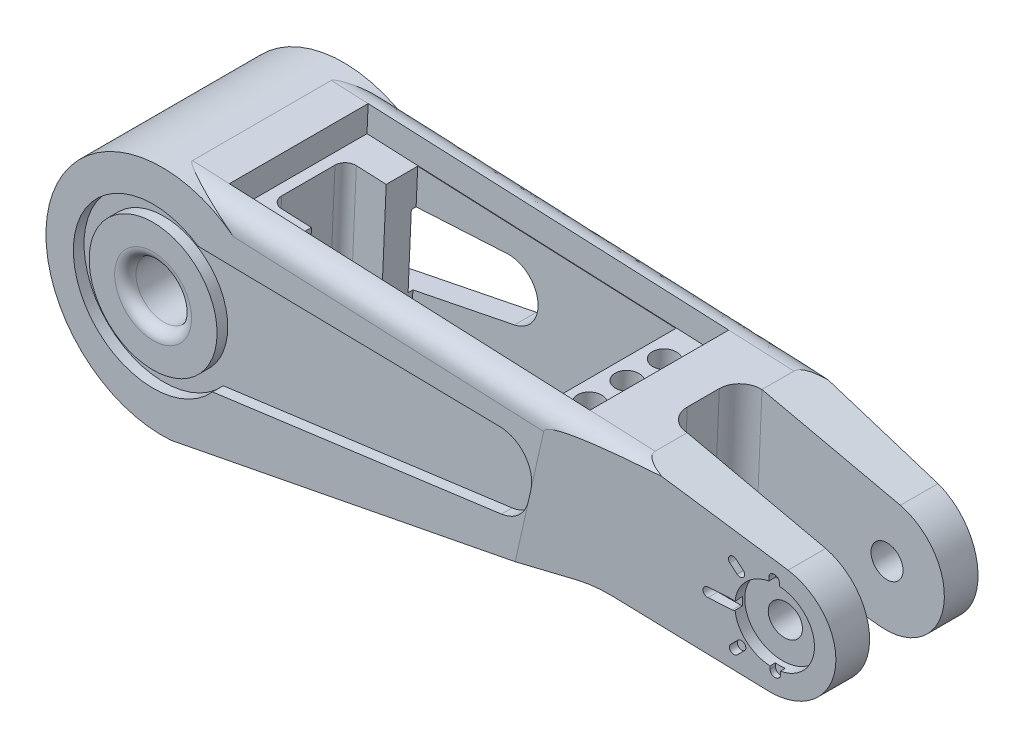
SolidWorks part; units mm, degrees
ref_plane "前视基准面" through (0, 0, 0) normal (0, 0, 1) x (1, 0, 0)
ref_plane "上视基准面" through (0, 0, 0) normal (0, 1, 0) x (1, 0, 0)
ref_plane "右视基准面" through (0, 0, 0) normal (1, 0, 0) x (0, 0, -1)
sketch "草图1" plane through (0, 0, 0) normal (0, 0, 1) x (1, 0, 0)
  line L2 (-19.4532, -0.6445) -> (19.7335, 6.9761)
  line L4 (-19.4532, 21.0492) -> (23.8765, 19.1407)
  line L9 (23.8765, 19.1407) -> (36.8454, 16.2397)
  line L10 (19.7335, 6.9761) -> (35.0831, 5.4643)
  circle A5 centre (-21.1408, 10.2023) radius 2.6 construction
  circle A6 centre (-21.1408, 10.2023) radius 2.6
  circle A7 centre (35.5914, 11.0768) radius 1.5
  arc A13 (35.0831, 5.4643) -> (36.8454, 16.2397) centre (35.4798, 10.9312) ccw
  arc A15 (-19.4532, 21.0492) -> (-19.4532, -0.6445) centre (-20.297, 10.2023) ccw
  dimension "D2" = 3
  dimension "D6" = 5.2
extrude "凸台-拉伸1" add sketch "草图1" along normal blind 17
sketch "草图5" plane through (0.8877, 20.1532, 0) normal (0.044, 0.999, 0) x (0.999, -0.044, 0)
  line L0 (-2.1258, -8.5) -> (9.9742, -8.5) construction
  line L1 (-12.1, -2.05) -> (12.1, -2.05)
  line L2 (-12.1, -2.05) -> (-12.1, -14.95) construction
  line L3 (-12.1, -14.95) -> (12.1, -14.95)
  line L4 (12.1, -2.05) -> (12.1, -14.95)
  line L5 (-12.1, -2.05) -> (12.1, -14.95) construction
  line L6 (-12.1, -14.95) -> (12.1, -2.05) construction
  line L7 (-14, -5) -> (14, -5) construction
  line L8 (-14, -5) -> (-14, -12) construction
  line L9 (-14, -12) -> (14, -12) construction
  line L10 (14, -5) -> (14, -12) construction
  line L11 (-14, -5) -> (14, -12) construction
  line L12 (-14, -12) -> (14, -5) construction
  line L13 (-12.1, -2.05) -> (-12.1, -5)
  line L14 (21.0181, -5) -> (64.762, -5)
  line L15 (21.0181, -5) -> (21.0181, -12)
  line L16 (21.0181, -12) -> (64.762, -12)
  line L17 (64.762, -5) -> (64.762, -12)
  line L18 (21.0181, -5) -> (64.762, -12) construction
  line L19 (21.0181, -12) -> (64.762, -5) construction
  line L20 (-15.9, -5) -> (-12.1, -5)
  line L21 (-15.9, -5) -> (-15.9, -12)
  line L22 (-15.9, -12) -> (-12.1, -12)
  line L23 (-12.1, -5) -> (-12.1, -12) construction
  line L24 (-15.9, -5) -> (-12.1, -12) construction
  line L25 (-15.9, -12) -> (-12.1, -5) construction
  line L26 (-12.1, -12) -> (-12.1, -14.95)
  line L27 (-25.9783, -8.5) -> (-22.2059, -8.5) construction
  circle A0 centre (-14, -5) radius 1.25 construction
  circle A1 centre (-14, -12) radius 1.25 construction
  circle A2 centre (14, -5) radius 1.15
  circle A3 centre (14, -12) radius 1.15
  circle A4 centre (-14, -8.5) radius 1.25 construction
  circle A5 centre (14, -8.5) radius 1.15
  point P0 (0, -8.5)
  point P5 (0, -8.5)
  point P23 (42.89, -8.5)
  dimension "D5" = 2.5
  dimension "D8" = 2.5
  dimension "D9" = 7
  dimension "D1" = 24.2
  dimension "D2" = 12.9
  dimension "D3" = 28
  dimension "D4" = 7
  dimension "D10" = 0
extrude "切除-拉伸2" cut sketch "草图5" against normal through all both and the other way through all
sketch "草图7" plane through (12.0883, -0.5324, 0) normal (-0.999, 0.044, 0) x (0, 0, 1)
  line L0 (2.05, 6.0797) -> (2.05, 20.1728) construction
  line L1 (2.05, 15.1728) -> (14.95, 15.1728)
  line L2 (2.05, 15.1728) -> (2.05, 3.1935)
  line L3 (2.05, 3.1935) -> (14.95, 3.1935)
  line L4 (14.95, 15.1728) -> (14.95, 3.1935)
  line L5 (14.95, 6.0797) -> (14.95, 20.1728) construction
  line L6 (2.05, 20.1728) -> (14.95, 20.1728) construction
  dimension "D1" = 5
extrude "切除-拉伸3" cut sketch "草图7" against normal blind 4
fillet "圆角2" radius 2 2 edges at (2.2116, 20.0949, 0) (2.2116, 20.0949, 17) conic rho 0.5
fillet "圆角3" radius 3 rebuild error yes
sketch "草图8" plane through (5.2154, 23.315, 0) normal (0.2183, 0.9759, 0) x (0.9759, -0.2183, 0)
  line L0 (11.1868, 0) -> (41.8849, -2.1466)
  line L1 (-17.391, 0) -> (30.5415, 0) construction
  line L2 (41.8849, -2.1466) -> (37.5658, 8.2117)
  line L3 (37.5658, 8.2117) -> (11.1868, 0)
  line L4 (11.2348, -17) -> (38.9022, -15.0653)
  line L5 (30.5415, -17) -> (-17.391, -17) construction
  line L6 (38.9022, -15.0653) -> (33.4878, -36.0011)
  line L7 (33.4878, -36.0011) -> (11.2348, -17)
  line L8 (32.4117, -17) -> (30.5415, -17) construction
  line L9 (36.3426, 0) -> (32.0305, 0) construction
  dimension "D1" = 4
  dimension "D2" = 4
extrude "切除-拉伸4" cut sketch "草图8" against normal through all both and the other way through all
sketch "草图9" plane through (0.8877, 20.1532, 0) normal (0.044, 0.999, 0) x (0.999, -0.044, 0)
  line L0 (23.0111, -2) -> (-20.3606, -2) construction
  line L1 (-16.9054, -2) -> (16.8949, -2)
  line L2 (-16.9054, -2) -> (-16.9054, -15)
  line L3 (-16.9054, -15) -> (16.8949, -15)
  line L4 (16.8949, -2) -> (16.8949, -15)
  line L5 (-20.3606, -15) -> (23.0111, -15) construction
extrude "切除-拉伸5" cut sketch "草图9" against normal blind 2.5
sketch "草图10" plane through (0, 0, 0) normal (0, 0, -1) x (-1, 0, 0)
  circle A0 centre (21.1408, 10.2023) radius 3.9889
  circle A1 centre (21.1408, 10.2023) radius 1.15
  dimension "D1" = 2.3
extrude "凸台-拉伸2" add sketch "草图10" against normal blind 9
sketch "草图11" plane through (0, 0, 0) normal (0, 0, -1) x (-1, 0, 0)
  line L4 (2.2472, 9.8443) -> (20.4137, 6.1927)
  line L5 (2.9414, 15.2862) -> (21.1408, 14.2773)
  circle A0 centre (21.1408, 10.2023) radius 4.075 construction
  circle A1 centre (2.7892, 12.5404) radius 2.75 construction
  arc A5 (2.9414, 15.2862) -> (2.2472, 9.8443) centre (2.7892, 12.5404) ccw
  arc A6 (21.1408, 14.2773) -> (20.4137, 6.1927) centre (21.1408, 10.2023) cw
  dimension "D1" = 8.15
  dimension "D3" = 5.5
  dimension "D2" = 18.5
extrude "切除-拉伸6" cut sketch "草图11" against normal blind 2.5
fillet "圆角5" radius 2 2 edges at (21.6121, 13.0232, 5) (21.6121, 13.0232, 12)
sketch "草图13" plane through (0, 0, 2.5) normal (0, 0, -1) x (-1, 0, 0)
  circle A0 centre (21.1408, 10.2023) radius 3.625
  dimension "D1" = 7.25
extrude "切除-拉伸7" cut sketch "草图13" against normal blind 1
fillet "圆角7" radius 1 1 edges at (-18.5408, 10.2023, 17)
fillet "圆角8" radius 11 1 edges at (19.7335, 6.9761, 8.5017)
sketch "草图16" plane through (0, 0, 17) normal (0, 0, 1) x (1, 0, 0)
  line L0 (15.0453, 15.7934) -> (-16.9221, 16.3666)
  line L1 (13.5523, 9.1193) -> (-15.5729, 5.223)
  line L2 (12.77, 5.6219) -> (15.4294, 17.5108) construction
  line L3 (15.0453, 15.7934) -> (13.5523, 9.1193)
  circle A0 centre (-21.1408, 10.2023) radius 5.9907
  circle A1 centre (-21.1408, 10.2023) radius 7.4697 construction
  arc A2 (-16.9221, 16.3666) -> (-15.5729, 5.223) centre (-21.1408, 10.2023) ccw
extrude "切除-拉伸8" cut sketch "草图16" against normal blind 1
fillet "圆角9" radius 3 2 edges at (13.5523, 9.1193, 16.5) (15.0453, 15.7934, 16.5)
sketch "草图17" plane through (1.2078, -0.2702, 17.6991) normal (0.0681, -0.0152, 0.9976) x (0.9977, 0.001, -0.0681)
  circle A0 centre (34.4635, 11.3125) radius 3.5
  dimension "D1" = 7
extrude "切除-拉伸9" cut sketch "草图17" against normal blind 1
sketch "草图18" plane through (0.0531, -0.0119, -0.7785) normal (0.0681, -0.0152, -0.9976) x (-0.9977, -0.001, -0.0681)
  circle A0 centre (-35.6209, 11.0529) radius 3.5
  dimension "D1" = 7
extrude "切除-拉伸10" cut sketch "草图18" against normal blind 1
fillet "圆角10" radius 1 2 edges at (-15.5102, 9.1996, 5) (-15.5102, 9.1996, 12)
sketch "草图19" plane through (0, 0, 16) normal (0, 0, 1) x (1, 0, 0)
  line L0 (-21.1408, 10.2023) -> (35.5981, 10.2023) construction
  line L1 (35.5981, 10.2023) -> (35.5981, 22.1291) construction
  line L2 (31.8727, 11.094) -> (29.7419, 11.094) construction
  line L3 (31.8727, 10.6598) -> (29.7419, 10.6598)
  line L4 (31.8727, 11.5282) -> (29.7419, 11.5282)
  line L5 (35.5981, 14.8624) -> (35.5981, 7.3257) construction
  line L6 (36.0598, 14.8624) -> (36.0598, 7.3257)
  line L7 (35.1364, 14.8624) -> (35.1364, 7.3257)
  line L8 (35.5981, 11.094) -> (31.9347, 14.7574) construction
  line L9 (35.5915, 11.0766) -> (32.6922, 8.1772) construction
  line L10 (32.6148, 8.0998) -> (31.9812, 7.4662) construction
  line L11 (32.9054, 7.8092) -> (32.2718, 7.1756)
  line L12 (32.3241, 8.3904) -> (31.6905, 7.7568)
  line L13 (32.6148, 14.0774) -> (31.9873, 14.7048) construction
  line L14 (32.3348, 13.7974) -> (31.7073, 14.4249)
  line L15 (32.8947, 14.3573) -> (32.2672, 14.9848)
  arc A0 (31.8727, 10.6598) -> (31.8727, 11.5282) centre (31.8727, 11.094) ccw
  arc A1 (29.7419, 11.5282) -> (29.7419, 10.6598) centre (29.7419, 11.094) ccw
  arc A2 (36.0598, 14.8624) -> (35.1364, 14.8624) centre (35.5981, 14.8624) ccw
  arc A3 (35.1364, 7.3257) -> (36.0598, 7.3257) centre (35.5981, 7.3257) ccw
  arc A4 (32.9054, 7.8092) -> (32.3241, 8.3904) centre (32.6148, 8.0998) ccw
  arc A5 (31.6905, 7.7568) -> (32.2718, 7.1756) centre (31.9812, 7.4662) ccw
  arc A6 (32.3348, 13.7974) -> (32.8947, 14.3573) centre (32.6148, 14.0774) ccw
  arc A7 (32.2672, 14.9848) -> (31.7073, 14.4249) centre (31.9873, 14.7048) ccw
  point P3 (30.8073, 11.094)
  point P14 (35.5981, 11.094)
  point P26 (32.298, 7.783)
  point P31 (32.301, 14.3911)
  dimension "D1" = 90
  dimension "D2" = 45
  dimension "D3" = 45
extrude "切除-拉伸11" cut sketch "草图19" against normal blind 1
